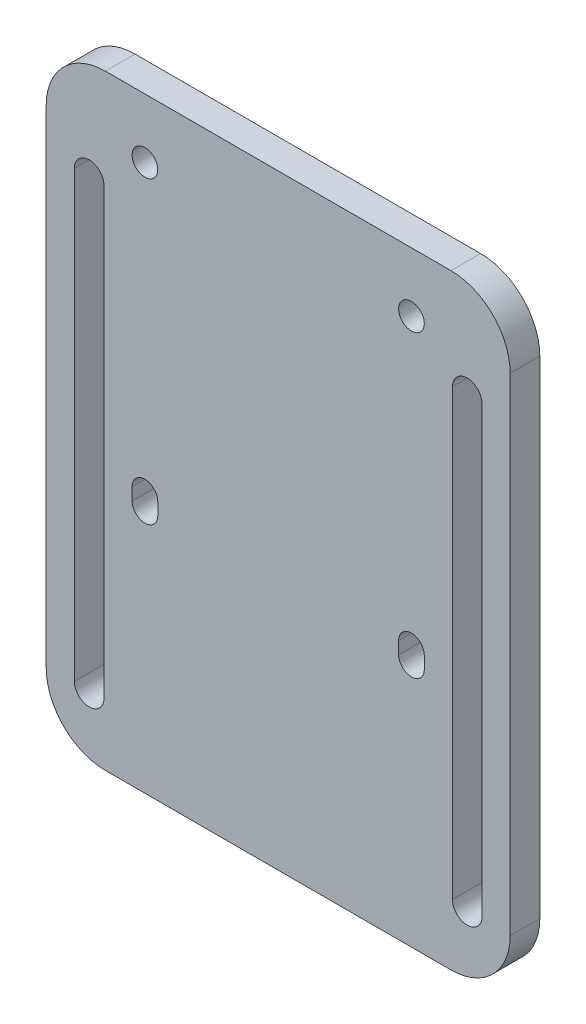
SolidWorks part; units mm, degrees
material "Acrylic (Medium-high impact)"
ref_plane "Спереди" through (0, 0, 0) normal (0, 0, 1) x (1, 0, 0)
ref_plane "Сверху" through (0, 0, 0) normal (0, 1, 0) x (1, 0, 0)
ref_plane "Справа" through (0, 0, 0) normal (1, 0, 0) x (0, 0, -1)
sketch "Model" plane through (0, 0, 0) normal (0, 0, 1) x (1, 0, 0)
  line L0 (0, 130.393) -> (0, -19.607) construction
  line L1 (38.3, 119.0065) -> (38.3, 3.8567) construction
  line L2 (39.6393, 110.7) -> (20.3566, 110.7) construction
  line L3 (27, 114.3973) -> (27, 106.7903) construction
  line L8 (27, 57.0366) -> (27, 46.0463) construction
  line L14 (-27, 114.3973) -> (-27, 106.7903) construction
  line L15 (-39.6393, 110.7) -> (-20.3566, 110.7) construction
  line L16 (-29.6, 50) -> (-29.6, 52.5)
  line L17 (-29.6, 52.5) -> (-29.6, 50)
  line L18 (-27, 57.0366) -> (-27, 46.0463) construction
  line L19 (-24.4, 52.5) -> (-24.4, 50)
  line L20 (-24.4, 50) -> (-24.4, 52.5)
  line L22 (-41.3, 12.5) -> (-41.3, 102.5)
  line L23 (-41.3, 102.5) -> (-41.3, 12.5)
  line L24 (-38.3, 119.0065) -> (-38.3, 3.8567) construction
  line L25 (-35.3, 102.5) -> (-35.3, 12.5)
  line L26 (-35.3, 12.5) -> (-35.3, 102.5)
  line L29 (-41.3, 12.5) -> (-35.3, 12.5) construction
  line L2974 (29.6, 52.5) -> (29.6, 50)
  line L2987 (24.4, 50) -> (24.4, 52.5)
  line L2994 (35.3, 12.5) -> (35.3, 102.5)
  line L3007 (41.3, 102.5) -> (41.3, 12.5)
  line L3504 (35, 0) -> (-35, 0)
  line L3511 (-47, 12) -> (-47, 110.7)
  line L3518 (-35, 122.7) -> (35, 122.7)
  line L3525 (47, 110.7) -> (47, 12)
  line L3777 (24.4, 52.5) -> (24.4, 50)
  line L3790 (29.6, 50) -> (29.6, 52.5)
  line L3887 (41.3, 12.5) -> (41.3, 102.5)
  line L3900 (35.3, 102.5) -> (35.3, 12.5)
  arc A0 (-47, 12) -> (-35, 0) centre (-35, 12) ccw
  arc A1 (35, 0) -> (47, 12) centre (35, 12) ccw
  arc A2 (47, 110.7) -> (35, 122.7) centre (35, 110.7) ccw
  arc A3 (-47, 110.7) -> (-35, 122.7) centre (-35, 110.7) cw
  circle A8 centre (27, 110.7) radius 2.6
  arc A9 (24.4, 52.5) -> (29.6, 52.5) centre (27, 52.5) cw
  arc A10 (24.4, 50) -> (29.6, 50) centre (27, 50) ccw
  arc A11 (35.3, 12.5) -> (41.3, 12.5) centre (38.3, 12.5) ccw
  arc A12 (35.3, 102.5) -> (41.3, 102.5) centre (38.3, 102.5) cw
  arc A17 (-35.3, 102.5) -> (-41.3, 102.5) centre (-38.3, 102.5) ccw
  circle A18 centre (-27, 110.7) radius 2.6
  arc A19 (-24.4, 50) -> (-29.6, 50) centre (-27, 50) cw
  arc A20 (-24.4, 52.5) -> (-29.6, 52.5) centre (-27, 52.5) ccw
  arc A22 (-35.3, 12.5) -> (-41.3, 12.5) centre (-38.3, 12.5) cw
  dimension "D1" = 12
  dimension "D17" = 5.2
  dimension "D22" = 2.6
  dimension "D23" = 2.6
  dimension "D26" = 90
  dimension "D6" = 54
  dimension "D2" = 70
  dimension "D3" = 122.7
  dimension "D4" = 76.6
  dimension "D5" = 58.2
  dimension "D7" = 54
  dimension "D20" = 2.5
  dimension "D21" = 5.2
  dimension "D24" = 50
  dimension "D25" = 6
  dimension "D27" = 12.5
extrude "Base" add sketch "Model" along normal blind 6 contours A3 L3511 A0 L3504 A1 L3525 A2 L3518 L25 A22 L22 A17 A20 L19 A19 L16 L2994 A12 L3007 A11 A8 A10 L2987 A9 L2974 region at (0, 61.6424, 0)
